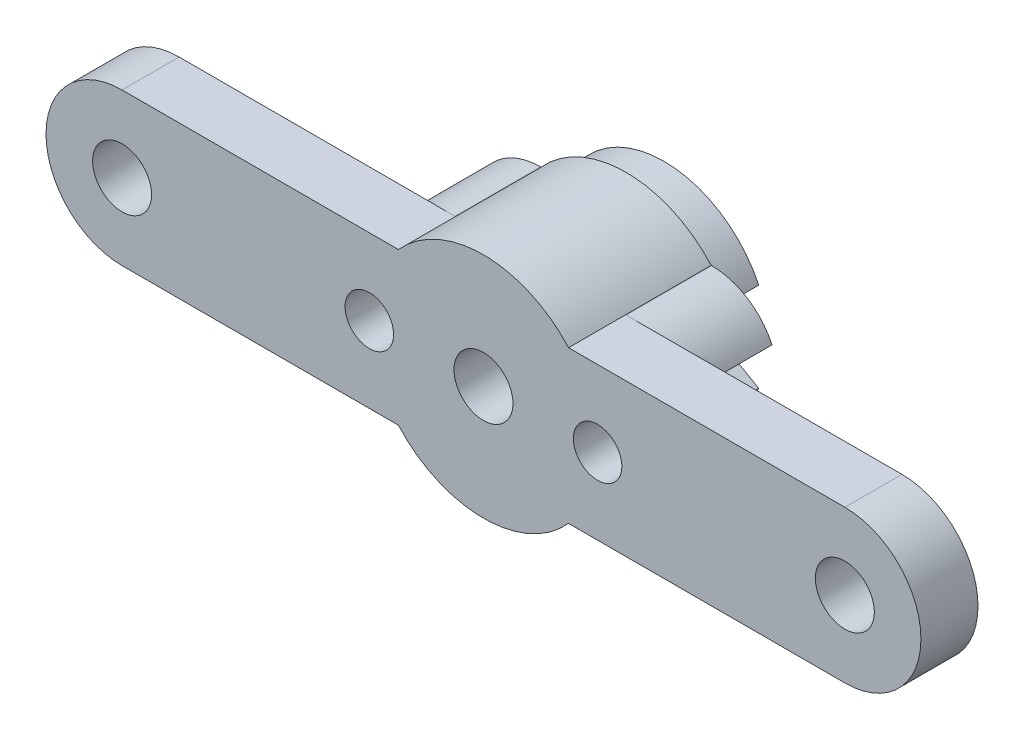
SolidWorks part; units mm, degrees
ref_plane "前视基准面" through (0, 0, 0) normal (0, 0, 1) x (1, 0, 0)
ref_plane "上视基准面" through (0, 0, 0) normal (0, 1, 0) x (1, 0, 0)
ref_plane "右视基准面" through (0, 0, 0) normal (1, 0, 0) x (0, 0, -1)
sketch "草图1" plane through (0, 0, 0) normal (0, 0, 1) x (1, 0, 0)
  line L0 (4.4721, 4) -> (19, 4)
  line L1 (-19, -4) -> (-4.4721, -4)
  line L2 (4.4721, -4) -> (19, -4)
  line L3 (-19, 4) -> (-4.4721, 4)
  circle A0 centre (0, 0) radius 1.55
  circle A1 centre (19, 0) radius 1.55
  circle A2 centre (-19, 0) radius 1.55
  arc A3 (-19, 4) -> (-19, -4) centre (-19, 0) ccw
  arc A4 (19, -4) -> (19, 4) centre (19, 0) ccw
  arc A5 (-4.4721, -4) -> (4.4721, -4) centre (0, 0) ccw
  arc A6 (4.4721, 4) -> (-4.4721, 4) centre (0, 0) ccw
  circle A7 centre (-6, 0) radius 1.275
  circle A8 centre (6, 0) radius 1.275
  dimension "D3" = 3.1
  dimension "D4" = 3.1
  dimension "D5" = 3.1
  dimension "D8" = 12
  dimension "D7" = 8
  dimension "D9" = 4
  dimension "D6" = 8
  dimension "D11" = 2.55
  dimension "D12" = 2.55
  dimension "D1" = 19
  dimension "D2" = 19
  dimension "D10" = 4
  dimension "D13" = 6
  dimension "D14" = 6
extrude "凸台-拉伸1" add sketch "草图1" along normal blind 3
sketch "草图2" plane through (0, 0, 0) normal (0, 0, -1) x (-1, 0, 0)
  line L0 (-19, 4) -> (-4.4721, 4) construction
  line L1 (-8, 4) -> (-4.4721, 4)
  line L2 (-8, 4) -> (-8, -4)
  line L3 (-8, -4) -> (-4.4721, -4)
  line L4 (8, 4) -> (8, -4)
  line L5 (19, -4) -> (4.4721, -4) construction
  line L6 (4.4721, 4) -> (8, 4)
  line L7 (4.4721, -4) -> (8, -4)
  arc A0 (-4.4721, -4) -> (4.4721, -4) centre (0, 0) ccw
  circle A2 centre (-6, 0) radius 1.275
  circle A3 centre (6, 0) radius 1.275
  arc A4 (4.4721, 4) -> (-4.4721, 4) centre (0, 0) ccw
  dimension "D1" = 2.55
  dimension "D2" = 12
  dimension "D3" = 2.55
  dimension "D4" = 8
  dimension "D5" = 8
extrude "凸台-拉伸2" add sketch "草图2" along normal blind 4.5
fillet "圆角1" radius 3.5 4 edges
sketch "草图3" plane through (0, 0, -4.5) normal (0, 0, -1) x (-1, 0, 0)
  circle A0 centre (0, 0) radius 5.5
  dimension "D1" = 11
extrude "凸台-拉伸3" add sketch "草图3" along normal blind 2
sketch "草图4" plane through (0, 0, -4.5) normal (0, 0, -1) x (-1, 0, 0)
  line L1 (-6, 2.9445) -> (-8.55, 1.4722)
  line L2 (-8.55, 1.4722) -> (-8.55, -1.4722)
  line L3 (-8.55, -1.4722) -> (-6, -2.9445)
  line L4 (-6, -2.9445) -> (-3.45, -1.4722)
  line L5 (-3.45, -1.4722) -> (-3.45, 1.4722)
  line L6 (-3.45, 1.4722) -> (-6, 2.9445)
  line L7 (8.4847, 1.4345) -> (6, 2.869)
  line L8 (6, 2.869) -> (3.5153, 1.4345)
  line L9 (3.5153, 1.4345) -> (3.5153, -1.4345)
  line L10 (3.5153, -1.4345) -> (6, -2.869)
  line L11 (6, -2.869) -> (8.4847, -1.4345)
  line L12 (8.4847, -1.4345) -> (8.4847, 1.4345)
  circle A0 centre (-6, 0) radius 2.55 construction
  circle A1 centre (6, 0) radius 2.4847 construction
sketch "草图5" plane through (0, 0, -6.5) normal (0, 0, -1) x (-1, 0, 0)
  circle A0 centre (0, 0) radius 2.6
  dimension "D1" = 5.2
sketch "草图7" plane through (0, 0, -6.5) normal (0, 0, -1) x (-1, 0, 0)
  circle A0 centre (0, 2.6) radius 0.4
  circle A1 centre (0, 0) radius 2.6 construction
  dimension "D1" = 0.8
extrude "切除-拉伸4" cut sketch "草图7" against normal blind 5 contours A0
pattern_circular "阵列(圆周)1" count 25 over 360 about axis through (0, 0, -6.5) along (0, 0, -1) of "切除-拉伸4"
extrude "切除-拉伸6" cut sketch "草图5" against normal blind 5
extrude "切除-拉伸7" cut sketch "草图4" against normal mid plane 8
sketch "草图8" plane through (0, 0, -1.5) normal (0, 0, -1) x (-1, 0, 0)
  circle A0 centre (0, 0) radius 1.55
  dimension "D1" = 3.1
extrude "切除-拉伸8" cut sketch "草图8" against normal blind 6
